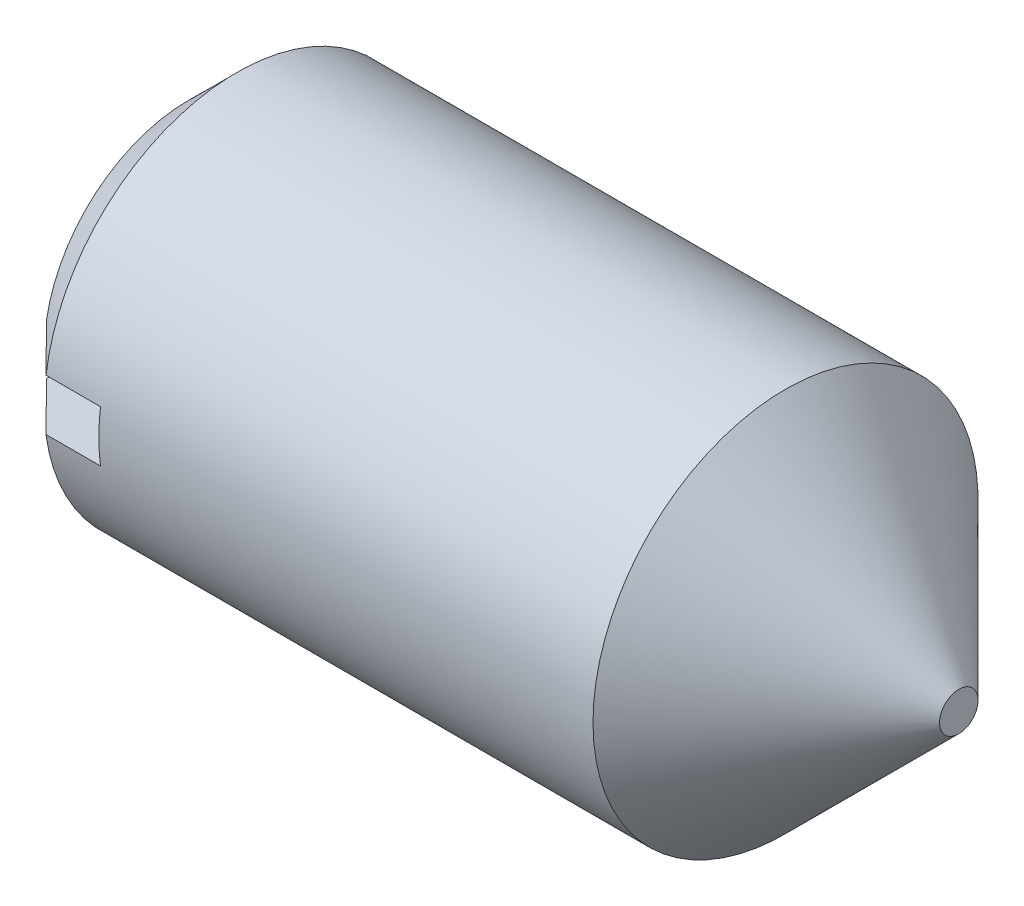
SolidWorks part; units mm, degrees
ref_plane "Front" through (0, 0, 0) normal (0, 0, 1) x (1, 0, 0)
ref_plane "Top" through (0, 0, 0) normal (0, 1, 0) x (1, 0, 0)
ref_plane "Right" through (0, 0, 0) normal (1, 0, 0) x (0, 0, -1)
sketch "Sketch1" plane through (0, 0, 0) normal (0, 0, 1) x (1, 0, 0)
  line L0 (0, 0) -> (6, 0)
  line L1 (6, 0) -> (6, 0.15)
  line L2 (6, 0.15) -> (4.65, 1.5)
  line L3 (4.65, 1.5) -> (0.375, 1.5)
  line L4 (0.375, 1.5) -> (0, 1.125)
  line L5 (0, 1.125) -> (0, 0)
  line L6 (-14.7741, 0) -> (12.5137, 0) construction
  dimension "D2" = 45
  dimension "D1" = 45
revolve "Base" add sketch "Sketch1" angle 360 about L6
cosmetic thread "ThreadCosmetic1" [suppressed] parameters "D2"=2.25
sketch "Sketch2" plane through (0, 0, 0) normal (0, 0, 1) x (1, 0, 0)
  line L1 (0, 0.2) -> (0.8, 0.2)
  line L2 (0, 0.2) -> (0, -0.2)
  line L3 (0, -0.2) -> (0.8, -0.2)
  line L4 (0.8, 0.2) -> (0.8, -0.2)
  line L5 (0, 1.125) -> (0, -1.125) construction
  dimension "m" = 0.2
extrude "Notch" cut sketch "Sketch2" against normal through all and the other way through all
sketch "Sketch3" plane through (0, 0, 0) normal (0, 0, 1) x (1, 0, 0)
  line L0 (0.375, 1.1752) -> (0.5625, 1.5)
  line L1 (0.5625, 1.5) -> (0.5625, 1.875)
  line L2 (0.5625, 1.875) -> (0.1875, 1.875)
  line L3 (0.1875, 1.875) -> (0.1875, 1.5)
  line L4 (0.1875, 1.5) -> (0.375, 1.1752)
  line L5 (0, 0) -> (2.4208, 0) construction
  line L6 (0.375, 1.5) -> (0.375, 0.2) construction
  dimension "D1" = 3
  dimension "D2" = 0.375
revolve "Cut-Revolve10" [suppressed] cut sketch "Sketch3" angle 360 about L5
pattern_linear "LPattern10" [suppressed] count 13 spacing 0.45 along (1, 0, 0) of bodies 103
equation "\"df@Sketch1\" = \"D2@ThreadCosmetic1\""
equation "\"m@Sketch2\" = \"n@Sketch2\" / 2"
equation "\"D1@Sketch3\" = \"d@Sketch1\""
equation "\"D2@Sketch3\" =  ( \"d@Sketch1\" - \"D2@ThreadCosmetic1\" )  / 2"
equation "\"D3@LPattern10\" = \"D2@Sketch3\" * 1.2"
equation "\"D1@LPattern10\" =  ( \"l@Sketch1\" -  ( \"d@Sketch1\" - \"df@Sketch1\" )  / 2 )  / \"D3@LPattern10\""
